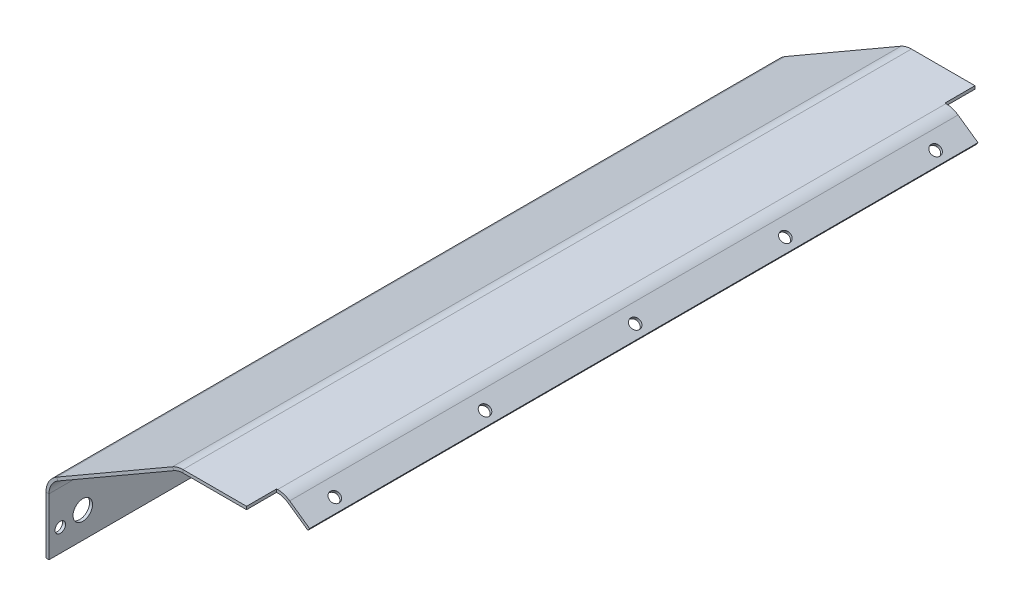
SolidWorks part; units mm, degrees
note: The reader was unsure of these and kept them because the rebuilt part matched: bend radius of "Basis-Blech1", "Basisbiegung1", "Basisbiegung2", "Basisbiegung3".
material "1.4301 (X5CrNi18-10)"
ref_plane "Vorne" through (0, 0, 0) normal (0, 0, 1) x (1, 0, 0)
ref_plane "Oben" through (0, 0, 0) normal (0, 1, 0) x (1, 0, 0)
ref_plane "Rechts" through (0, 0, 0) normal (1, 0, 0) x (0, 0, -1)
sketch "Skizze1" plane through (0, 0, 0) normal (0, 0, 1) x (1, 0, 0)
  line L0 (0, -22.5) -> (0, 22.5)
  line L1 (0, 22.5) -> (86, 72.1521)
  line L2 (86, 72.1521) -> (136, 72.1521)
  line L3 (136, 72.1521) -> (152.383, 60.6806)
  point P1 (0, 0)
  dimension "D3" = 20
  dimension "D4" = 50
  dimension "D5" = 86
  dimension "D6" = 49.6521
  dimension "D1" = 145
  dimension "D2" = 150
  dimension "D7" = 45
sheet metal parameters "Blech1" thickness 2 parameters "D1"=12
base flange "Basis-Blech1" sketch "Skizze1" end condition mid plane depth 485 reverse direction no thickness 2 reverse thickness direction yes bend radius 12
bend "Basisbiegung1" bend radius 12 bend angle 35 parameters "D5"=1
bend "Basisbiegung2" bend radius 12 bend angle 30 parameters "D5"=2
bend "Basisbiegung3" bend radius 12 bend angle 60 parameters "D5"=3
sketch "Skizze4" plane through (0, 74.1521, 0) normal (0, 1, 0) x (1, 0, 0)
  line L0 (89.2154, 242.5) -> (132.2164, 242.5) construction
  line L1 (131.5302, 242.5) -> (153.5302, 242.5)
  line L2 (131.5302, 242.5) -> (131.5302, 222.5)
  line L3 (131.5302, 222.5) -> (153.5302, 222.5)
  line L4 (153.5302, 242.5) -> (153.5302, 222.5)
  line L5 (153.5302, -242.5) -> (153.5302, 242.5) construction
  line L6 (89.2154, -242.5) -> (132.2164, -242.5) construction
  line L7 (131.5302, -242.5) -> (153.5302, -242.5)
  line L8 (131.5302, -242.5) -> (131.5302, -222.5)
  line L9 (131.5302, -222.5) -> (153.5302, -222.5)
  line L10 (153.5302, -242.5) -> (153.5302, -222.5)
  dimension "D1" = 445
  dimension "D2" = 22
extrude "Schnitt-Linear austragen1" cut sketch "Skizze4" against normal through all normal cut yes
hole_wizard "Ø7.0 (7) Durchmesser Bohrung1" positions "Skizze6" profile "Skizze5" hole size "Ø7.0" standard "Gabler-Normteile" end condition through all
sketch "Skizze6" plane through (-2, 72.1521, 0) normal (1, 0, 0) x (0, -1, 0)
  line L3 (94.6521, 242.5) -> (56.5803, 242.5) construction
  line L4 (94.6521, -242.5) -> (94.6521, 242.5) construction
  point P0 (79.6521, -235)
  point P2 (79.6521, 235)
  dimension "D1" = 7.5
  dimension "D2" = 470
  dimension "D3" = 15
sketch "Skizze5" plane through (-2, -7.5, 235) normal (0, 1, 0) x (0, 0, 1)
  line L0 (0, 0) -> (0, 155.5302)
  line L1 (0, 155.5302) -> (3.5, 155.5302)
  line L2 (3.5, 155.5302) -> (3.5, 0)
  line L5 (3.5, 0) -> (0, 0)
  line L11 (0, -6.35) -> (0, 107.95) construction
  dimension "Bohrerdurchmesser" = 7
  dimension "Bohrungstiefe" = 155.5302
hole_wizard "Ø13.0 (13) Durchmesser Bohrung1" positions "Skizze8" profile "Skizze7" hole size "Ø13.0" standard "Gabler-Normteile" end condition through all
sketch "Skizze8" plane through (-2, 0, 0) normal (-1, 0, 0) x (0, 0, 1)
  line L0 (-242.5, -22.5) -> (-242.5, 15.5718) construction
  line L1 (242.5, -22.5) -> (-242.5, -22.5) construction
  point P0 (-220, -5)
  point P2 (220, -5)
  dimension "D1" = 22.5
  dimension "D2" = 440
  dimension "D3" = 17.5
sketch "Skizze7" plane through (-2, -5, -220) normal (0, 1, 0) x (0, 0, 1)
  line L0 (0, 0) -> (0, 155.5302)
  line L1 (0, 155.5302) -> (6.5, 155.5302)
  line L2 (6.5, 155.5302) -> (6.5, 0)
  line L5 (6.5, 0) -> (0, 0)
  line L11 (0, -6.35) -> (0, 107.95) construction
  dimension "Bohrerdurchmesser" = 13
  dimension "Bohrungstiefe" = 155.5302
hole_wizard "Ø7.0 (7) Durchmesser Bohrung2" positions "Skizze11" profile "Skizze10" hole size "Ø7.0" standard "Gabler-Normteile" end condition through all
sketch "Skizze11" plane through (79.7902, 113.9522, 0) normal (0.5736, 0.8192, 0) x (0, 0, -1)
  line L0 (-222.5, -90.0199) -> (222.5, -90.0199) construction
  line L1 (0, 0) -> (0, -83.0199) construction
  point P0 (0, -83.0199)
  point P2 (-100, -83.0199)
  point P4 (-200, -83.0199)
  point P6 (100, -83.0199)
  point P8 (200, -83.0199)
  dimension "D1" = 7
  dimension "D2" = 100
  dimension "D3" = 100
sketch "Skizze10" plane through (147.7961, 66.3339, 0) normal (0, 0, 1) x (-0.8192, 0.5736, 0)
  line L0 (0, 0) -> (0, 158.688)
  line L1 (0, 158.688) -> (3.5, 158.688)
  line L2 (3.5, 158.688) -> (3.5, 0)
  line L5 (3.5, 0) -> (0, 0)
  line L11 (0, -6.35) -> (0, 107.95) construction
  dimension "Bohrerdurchmesser" = 7
  dimension "Bohrungstiefe" = 158.688
flat pattern "Abwicklung1" [suppressed]
sketch "Biegung-Linien1" plane through (-10.7428, 18.6071, 0) normal (-0.5, 0.866, 0) x (0.866, 0.5, 0)
  line L0 (11.3714, -242.5) -> (11.3714, 242.5) construction
  line L1 (110.7422, 242.5) -> (110.7422, -242.5) construction
  line L2 (161.1173, 222.5) -> (161.1173, -222.5) construction
sketch3d "Rahmen1" [suppressed]
  line L0 (-44.7572, 0, 0) -> (-44.7572, 485, 0) construction
  line L1 (170.0543, 0, 0) -> (170.0543, 485, 0) construction
  line L2 (-44.7572, 0, 0) -> (170.0543, 0, 0) construction
  line L3 (-44.7572, 485, 0) -> (170.0543, 485, 0) construction
